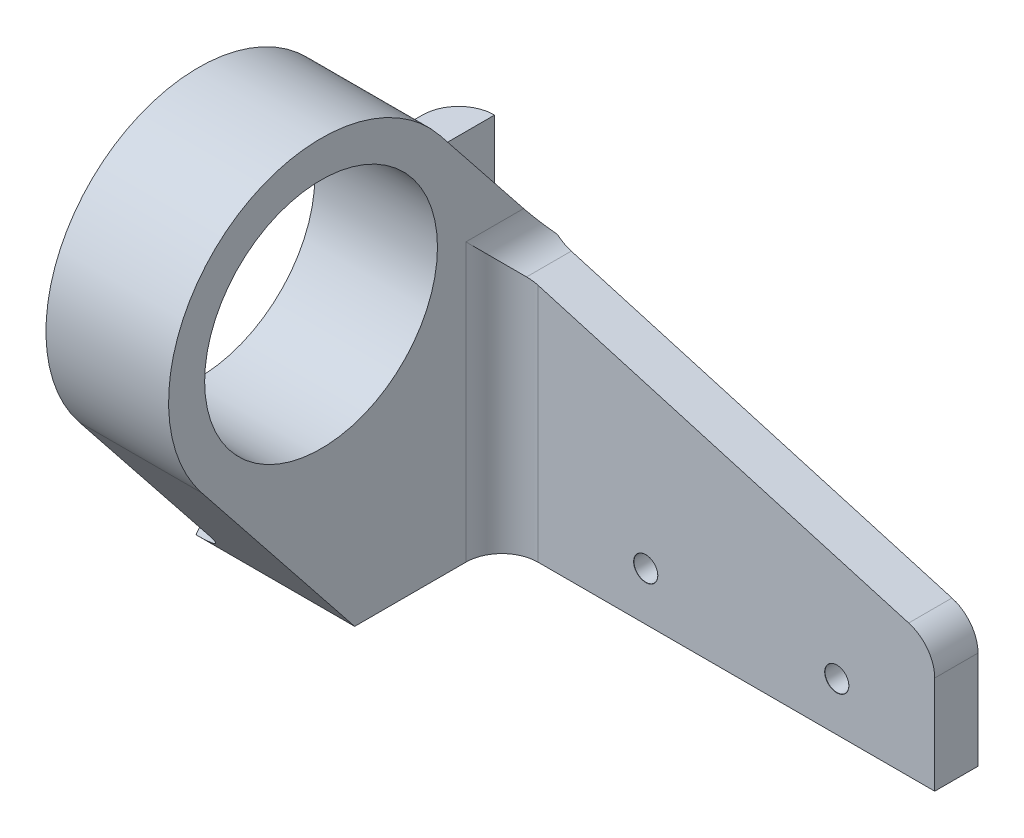
SolidWorks part; units mm, degrees
ref_plane "Front Plane" through (0, 0, 0) normal (0, 0, 1) x (1, 0, 0)
ref_plane "Top Plane" through (0, 0, 0) normal (0, 1, 0) x (1, 0, 0)
ref_plane "Right Plane" through (0, 0, 0) normal (1, 0, 0) x (0, 0, -1)
sketch "Sketch1" plane through (0, 0, 0) normal (1, 0, 0) x (0, 0, -1)
  circle A0 centre (0, 0) radius 16.14
  circle A1 centre (0, 0) radius 21.14
  dimension "D1" = 32.28
  dimension "D2" = 5
extrude "Boss-Extrude1" add sketch "Sketch1" along normal blind 17
sketch "Sketch2" plane through (0, 0, 0) normal (-1, 0, 0) x (0, 0, 1)
  line L0 (-31.0807, -39.7984) -> (-31.0807, -5.0984)
  line L1 (-31.0807, -5.0984) -> (-16.5386, 13.1672)
  line L2 (-31.0807, -39.7984) -> (-4.6638, -39.7984)
  line L3 (-36.0807, -39.7984) -> (-246.0807, -39.7984) construction
  line L4 (-4.6638, -39.7984) -> (16.5386, -13.1672)
  circle A0 centre (0, 0) radius 21.14 construction
  arc A1 (-16.5386, 13.1672) -> (16.5386, -13.1672) centre (0, 0) ccw
extrude "Boss-Extrude2" add sketch "Sketch2" against normal up to surface (17 mm away) up to face at (17, 0, -21.14)
sketch "Sketch3" plane through (17, 0, 0) normal (1, 0, 0) x (0, 0, -1)
  line L0 (31.0807, -5.0984) -> (31.0807, -39.7984) construction
  line L1 (31.0807, -5.0984) -> (25.0807, -5.0984)
  line L2 (31.0807, -5.0984) -> (31.0807, -39.7984)
  line L3 (31.0807, -39.7984) -> (25.0807, -39.7984)
  line L4 (25.0807, -5.0984) -> (25.0807, -39.7984)
  line L5 (31.0807, -39.7984) -> (4.6638, -39.7984) construction
  line L6 (31.0807, -34.7984) -> (31.0807, 18.2327) construction
  dimension "D1" = 6
extrude "Boss-Extrude3" add sketch "Sketch3" along normal blind 60
sketch "Sketch4" plane through (0, 0, -25.0807) normal (0, 0, 1) x (1, 0, 0)
  line L0 (17, -5.0984) -> (77, -22.4484)
  line L1 (77, -5.0984) -> (77, -39.7984) construction
  line L2 (77, -5.0984) -> (17, -5.0984) construction
  line L3 (77, -5.0984) -> (77, -22.4484)
  line L4 (77, -5.0984) -> (17, -5.0984)
extrude "Cut-Extrude1" cut sketch "Sketch4" against normal blind 30
fillet "Fillet1" radius 5 3 edges at (17, -22.4484, -25.0807) (77, -22.4484, -28.0807) (17, -5.0984, -28.0807)
sketch "Sketch5" plane through (0, 0, 0) normal (-1, 0, 0) x (0, 0, 1)
  line L0 (-36.0807, -39.7984) -> (-246.0807, -39.7984) construction
  line L1 (-31.0807, -5.0984) -> (-41.0665, -5.0984)
  line L3 (-25.5019, -39.7984) -> (-41.0665, -39.7984)
  line L4 (-41.0665, -5.0984) -> (-41.0665, -39.7984)
  line L5 (-31.0807, -5.0984) -> (-4.6638, -39.7984)
  line L6 (-31.0807, -5.0984) -> (-31.0807, -39.7984) construction
  line L7 (-4.6638, -39.7984) -> (-25.5019, -39.7984)
extrude "Boss-Extrude4" add sketch "Sketch5" along normal blind 5
fillet "Fillet2" radius 5 2 edges at (-5, -22.4484, -41.0665) (0, -22.4484, -17.8723)
hole_wizard "Tap Drill for M4x0.7 Tap1" positions "Sketch6" profile "Sketch7" hole size "M4x0.7" standard "ANSI Metric"
sketch "Sketch6" plane through (-5, 0, 0) normal (-1, 0, 0) x (0, 0, 1)
  point P0 (-35.1563, -14.7013)
  point P2 (-35.1563, -34.1067)
sketch "Sketch7" plane through (-5, -14.7013, -35.1563) normal (0, 1, 0) x (0, 0, 1)
  line L0 (0, 0) -> (0, 5.9914)
  line L1 (0, 5.9914) -> (1.65, 5)
  line L2 (1.65, 5) -> (1.65, 0.021)
  line L3 (1.65, 0.021) -> (1.675, 0)
  line L5 (1.675, 0) -> (0, 0)
  line L6 (-1.65, 0.021) -> (-1.675, 0) construction
  line L10 (0, 5.9914) -> (-1.65, 5) construction
  line L11 (0, -6.35) -> (0, 107.95) construction
  dimension "Hole Dia." = 3.3
  dimension "Hole Depth" = 5
  dimension "Near C'Sink Dia." = 3.35
  dimension "Near C'Sink Angle" = 100
  dimension "Drill Angle" = 118
hole_wizard "Tap Drill for M4x0.7 Tap2" positions "Sketch8" profile "Sketch9" hole size "M4x0.7" standard "ANSI Metric"
sketch "Sketch8" plane through (0, 0, -25.0807) normal (0, 0, 1) x (1, 0, 0)
  point P0 (36.9326, -33.0951)
  point P2 (63.4184, -33.0951)
sketch "Sketch9" plane through (36.9326, -33.0951, -25.0807) normal (1, 0, 0) x (0, -1, 0)
  line L0 (0, 0) -> (0, 7.9914)
  line L1 (0, 7.9914) -> (1.65, 7)
  line L2 (1.65, 7) -> (1.65, 0.021)
  line L3 (1.65, 0.021) -> (1.675, 0)
  line L5 (1.675, 0) -> (0, 0)
  line L6 (-1.65, 0.021) -> (-1.675, 0) construction
  line L10 (0, 7.9914) -> (-1.65, 7) construction
  line L11 (0, -6.35) -> (0, 107.95) construction
  dimension "Hole Dia." = 3.3
  dimension "Hole Depth" = 7
  dimension "Near C'Sink Dia." = 3.35
  dimension "Near C'Sink Angle" = 100
  dimension "Drill Angle" = 118
